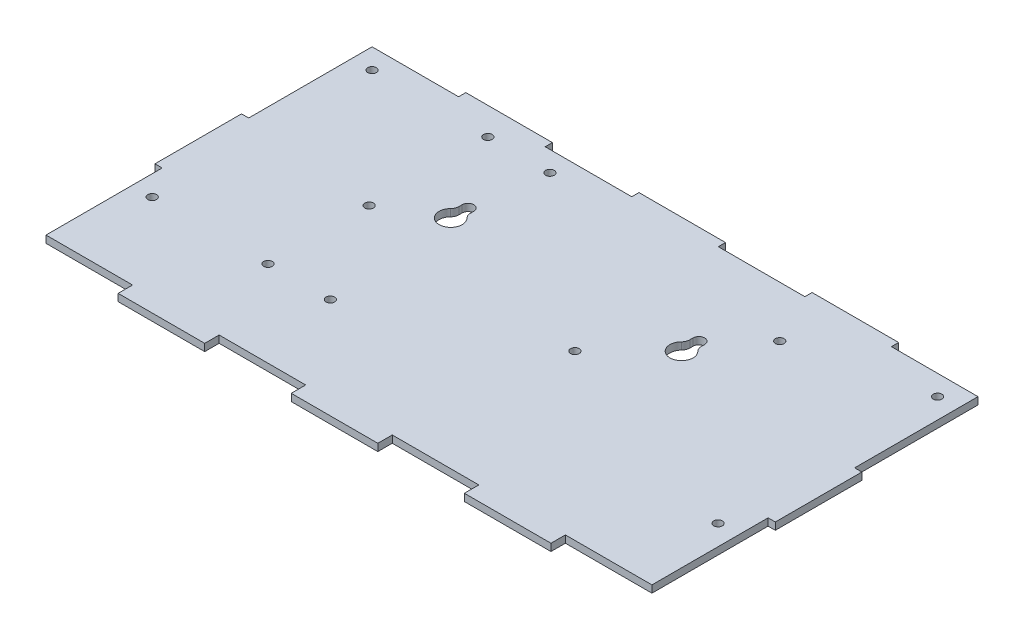
SolidWorks part; units mm, degrees
material "Maple"
ref_plane "Front Plane" through (0, 0, 0) normal (0, 0, 1) x (1, 0, 0)
ref_plane "Top Plane" through (0, 0, 0) normal (0, 1, 0) x (1, 0, 0)
ref_plane "Right Plane" through (0, 0, 0) normal (1, 0, 0) x (0, 0, -1)
sketch "Sketch2" plane through (0, 0, 0) normal (0, 1, 0) x (1, 0, 0)
  line L0 (-107.5, -60.25) -> (-107.5, 60.25) construction
  line L1 (-109.5, -62.25) -> (109.5, -62.25)
  line L2 (-109.5, -62.25) -> (-109.5, 62.25)
  line L3 (-109.5, 62.25) -> (109.5, 62.25)
  line L4 (109.5, -62.25) -> (109.5, 62.25)
  line L5 (-109.5, -62.25) -> (109.5, 62.25) construction
  line L6 (-109.5, 62.25) -> (109.5, -62.25) construction
  line L7 (-107.5, 60.25) -> (107.5, 60.25) construction
  line L8 (107.5, -60.25) -> (107.5, 60.25) construction
  line L9 (-107.5, -60.25) -> (107.5, -60.25) construction
  line L10 (0, 62.25) -> (0, -62.25) construction
  line L11 (-109.5, 0) -> (109.5, 0) construction
  line L12 (45, 57.75) -> (45, 60.25)
  line L13 (105, -15) -> (107.5, -15)
  line L14 (105, -15) -> (105, 15)
  line L15 (105, 15) -> (107.5, 15)
  line L16 (107.5, -15) -> (107.5, 15)
  line L17 (105, -15) -> (107.5, 15) construction
  line L18 (105, 15) -> (107.5, -15) construction
  line L19 (-15, 57.75) -> (15, 57.75)
  line L20 (-15, 57.75) -> (-15, 60.25)
  line L21 (-15, 60.25) -> (15, 60.25)
  line L22 (15, 57.75) -> (15, 60.25)
  line L23 (-15, 57.75) -> (15, 60.25) construction
  line L24 (-15, 60.25) -> (15, 57.75) construction
  line L25 (45, 57.75) -> (75, 57.75)
  line L26 (75, 57.75) -> (75, 60.25)
  line L27 (45, 60.25) -> (75, 60.25)
  line L28 (-45, 57.75) -> (-75, 57.75)
  line L29 (-75, 57.75) -> (-75, 60.25)
  line L30 (-45, 60.25) -> (-75, 60.25)
  line L31 (-45, 57.75) -> (-45, 60.25)
  line L32 (-15, -60.25) -> (15, -60.25)
  line L33 (15, -57.75) -> (15, -60.25)
  line L34 (-15, -57.75) -> (15, -57.75) construction
  line L35 (-15, -57.75) -> (-15, -60.25)
  line L36 (45, -57.75) -> (75, -57.75) construction
  line L37 (75, -57.75) -> (75, -60.25)
  line L38 (45, -60.25) -> (75, -60.25)
  line L39 (45, -57.75) -> (45, -60.25)
  line L40 (-45, -57.75) -> (-45, -60.25)
  line L41 (-45, -60.25) -> (-75, -60.25)
  line L42 (-75, -57.75) -> (-75, -60.25)
  line L43 (-45, -57.75) -> (-75, -57.75) construction
  line L44 (-105, 15) -> (-107.5, 15)
  line L45 (-107.5, -15) -> (-107.5, 15)
  line L46 (-105, -15) -> (-107.5, -15)
  line L47 (-105, -15) -> (-105, 15)
  line L48 (-15, -57.75) -> (-15, -55.25)
  line L49 (-75, -57.75) -> (-45, -57.75) construction
  line L50 (-75, -57.75) -> (-75, -55.25)
  line L51 (-75, -55.25) -> (-45, -55.25)
  line L52 (-45, -57.75) -> (-45, -55.25)
  line L53 (-15, -55.25) -> (15, -55.25)
  line L54 (15, -57.75) -> (15, -55.25)
  line L55 (45, -57.75) -> (45, -55.25)
  line L56 (45, -55.25) -> (75, -55.25)
  line L57 (75, -57.75) -> (75, -55.25)
  line L58 (-105, -15) -> (-105, -62.25)
  line L59 (-105, 15) -> (-105, 62.25)
  line L60 (105, -15) -> (105, -62.25)
  line L61 (105, 15) -> (105, 62.25)
  line L63 (-105, 57.75) -> (105, 57.75)
  line L64 (-105, 57.75) -> (-105, -55.25)
  line L65 (-105, -55.25) -> (105, -55.25)
  line L66 (105, 57.75) -> (105, -55.25)
  circle A0 centre (17.014, -26.7486) radius 5.75 construction
  circle A1 centre (-0.0002, -43.7628) radius 5.75 construction
  circle A2 centre (-17.0144, -26.7486) radius 5.75 construction
  circle A3 centre (-0.0002, -9.7344) radius 5.75 construction
  circle A4 centre (-0.0002, -43.7628) radius 5.75
  circle A5 centre (-17.0144, -26.7486) radius 5.75
  circle A6 centre (-0.0002, -9.7344) radius 5.75
  circle A7 centre (17.014, -26.7486) radius 5.75
  point P0 (0, 0)
  point P14 (106.25, 0)
  point P19 (0, 59)
  dimension "D8" = 3
  dimension "D1" = 124.5
  dimension "D2" = 219
  dimension "D4" = 30
  dimension "D5" = 2.5
  dimension "D7" = 30
  dimension "D9" = 30
  dimension "D3" = 2
  dimension "D6" = 2
extrude "Boss-Extrude1" [suppressed] add sketch "Sketch2" along normal mid plane 2.5 contours L58 L65 L51 L53 L56 L60 L14 L61 L63 L25 L19 L28 L59 L47 A7 A6 A5 A4 | L44 L59 L3 L2 L1 L58 L46 L45 | L59 L63 L29 L30 L31 L20 L21 L22 L12 L27 L26 L61 L3 | L65 L58 L1 L60 L57 L37 L38 L39 L55 L54 L33 L32 L35 L48 L52 L40 L41 L42 L50 | L61 L15 L16 L13 L60 L1 L4 L3
fillet "Fillet1" [suppressed] radius 2
sketch "Sketch3" [suppressed] plane through (0, 1.25, 0) normal (0, 1, 0) x (1, 0, 0)
  line L0 (-7.2123, 19.16) -> (7.6999, 19.16) construction
  line L1 (-35.6, 7.16) -> (35.6, 7.16)
  line L2 (-35.6, 7.16) -> (-35.6, 31.16)
  line L3 (-35.6, 31.16) -> (35.6, 31.16)
  line L4 (35.6, 7.16) -> (35.6, 31.16)
  line L5 (-35.6, 7.16) -> (35.6, 31.16) construction
  line L6 (-35.6, 31.16) -> (35.6, 7.16) construction
  line L13 (-107.5, -62.25) -> (107.5, -62.25) construction
  line L14 (0, 23.25) -> (0, 7.75) construction
  circle A2 centre (-37.37, 35.16) radius 1.5
  circle A3 centre (-37.37, 4.16) radius 1.5
  circle A4 centre (-21.7395, -5.84) radius 1.5
  circle A5 centre (-21.7395, -47.75) radius 1.5
  circle A6 centre (21.7395, -47.75) radius 1.5
  circle A7 centre (21.7395, -5.84) radius 1.5
  circle A8 centre (37.37, 4.16) radius 1.5
  circle A9 centre (37.37, 35.16) radius 1.5
  point P0 (0, 19.16)
  dimension "D7" = 3
  dimension "D1" = 71.2
  dimension "D2" = 24
  dimension "D3" = 4
  dimension "D6" = 14.5
  dimension "D9" = 3
  dimension "D10" = 1.77
  dimension "D12" = 41.91
  dimension "D13" = 43.479
  dimension "D14" = 10
  dimension "D11" = 2
extrude "Cut-Extrude1" [suppressed] cut sketch "Sketch3" against normal blind 10
sketch "Sketch4" [suppressed] plane through (0, 1.25, 0) normal (0, 1, 0) x (1, 0, 0)
  line L0 (-60.1289, 41.16) -> (60.1289, 41.16) construction
  line L2 (35.6, 31.16) -> (-35.6, 31.16) construction
  text T0 "Tank Level Control" font "Century Gothic" height 10
  point P2 (0, 41.16)
  dimension "D1" = 10
extrude "Cut-Extrude2" [suppressed] cut sketch "Sketch4" against normal blind 0.5
extrude "Boss-Extrude2" add sketch "Sketch2<4>" along normal mid plane 2.5 contours A4 | A7 | A5 | A6 | L46 L47 L44 L45 | L13 L16 L15 L14 | L58 L65 L51 L53 L56 L60 L14 L61 L63 L25 L19 L28 L59 L47 A7 A6 A5 A4 | L28 L31 L30 L29 | L19 L22 L21 L20 | L37 L57 L56 L55 L39 L38 | L33 L54 L53 L48 L35 L32 | L40 L52 L51 L50 L42 L41 | L25 L26 L27 L12 region at (0, 0, -1.7489) region at (-106.25, 0, 0) region at (-60, 0, 57.75) region at (106.25, 0, 0) region at (60, 0, 57.75) region at (-60, 0, -59) region at (0, 0, 57.75) region at (0, 0, -59) region at (-0.0002, 0, 43.7628) region at (-17.0144, 0, 26.7486) region at (-0.0002, 0, 9.7344) region at (17.014, 0, 26.7486)
sketch "Sketch2<4>" plane through (0, 0, 0) normal (0, 1, 0) x (1, 0, 0) same geometry as "Sketch2"
sketch "Sketch5" plane through (0, 1.25, 0) normal (0, 1, 0) x (1, 0, 0)
  line L3 (0, 28.1925) -> (0, -17.4495) construction
  line L4 (40, 26) -> (40, 20) construction
  line L5 (-40, 26) -> (-40, 21.6804) construction
  line L6 (-38, 26) -> (-38, 24.899)
  line L7 (-42, 26) -> (-42, 24.899)
  line L8 (-40, 26) -> (-40, 20) construction
  line L9 (40, 26) -> (40, 21.6804) construction
  line L10 (42, 26) -> (42, 24.899)
  line L11 (38, 26) -> (38, 24.899)
  line L12 (-57.87, -25.45) -> (-57.87, 50.75) construction
  line L13 (-105, 57.75) -> (-105, 15) construction
  line L14 (105, 57.75) -> (105, 15) construction
  line L15 (75, 57.75) -> (105, 57.75) construction
  circle A0 centre (98, 50.75) radius 1.5
  circle A1 centre (-36.37, 50.75) radius 1.5
  circle A2 centre (-36.37, -25.32) radius 1.5
  circle A3 centre (98, -25.32) radius 1.5
  circle A4 centre (53.99, 40.05) radius 1.5
  circle A5 centre (21.48, 1.57) radius 1.5
  circle A6 centre (-98, 50.75) radius 1.5
  circle A7 centre (-57.87, 50.75) radius 1.5
  circle A8 centre (-98, -25.45) radius 1.5
  circle A9 centre (-57.87, -25.45) radius 1.5
  arc A26 (-42.8571, 22.7994) -> (-37.1429, 22.7994) centre (-40, 20) ccw
  arc A27 (-38, 26) -> (-42, 26) centre (-40, 26) ccw
  arc A29 (-42, 24.899) -> (-42.8571, 22.7994) centre (-45, 24.899) cw
  arc A30 (-38, 24.899) -> (-37.1429, 22.7994) centre (-35, 24.899) ccw
  arc A31 (38, 24.899) -> (37.1429, 22.7994) centre (35, 24.899) cw
  arc A32 (42, 24.899) -> (42.8571, 22.7994) centre (45, 24.899) ccw
  arc A33 (38, 26) -> (42, 26) centre (40, 26) cw
  arc A34 (42.8571, 22.7994) -> (37.1429, 22.7994) centre (40, 20) cw
  circle A35 centre (-57.87, 9.6) radius 1.5
  point P32 (-40, 24)
  point P52 (40, 24)
  dimension "D2" = 3
  dimension "D13" = 20
  dimension "D14" = 40
  dimension "D17" = 2
  dimension "D18" = 8
  dimension "D19" = 3
  dimension "D3" = 7
  dimension "D4" = 76.07
  dimension "D5" = 134.37
  dimension "D6" = 10.7
  dimension "D7" = 44.01
  dimension "D8" = 76.52
  dimension "D9" = 26.89
  dimension "D10" = 40.13
  dimension "D11" = 7
  dimension "D12" = 76.2
  dimension "D15" = 6
  dimension "D16" = 41.15
  dimension "D20" = 7
extrude "Cut-Extrude3" cut sketch "Sketch5" against normal through all
